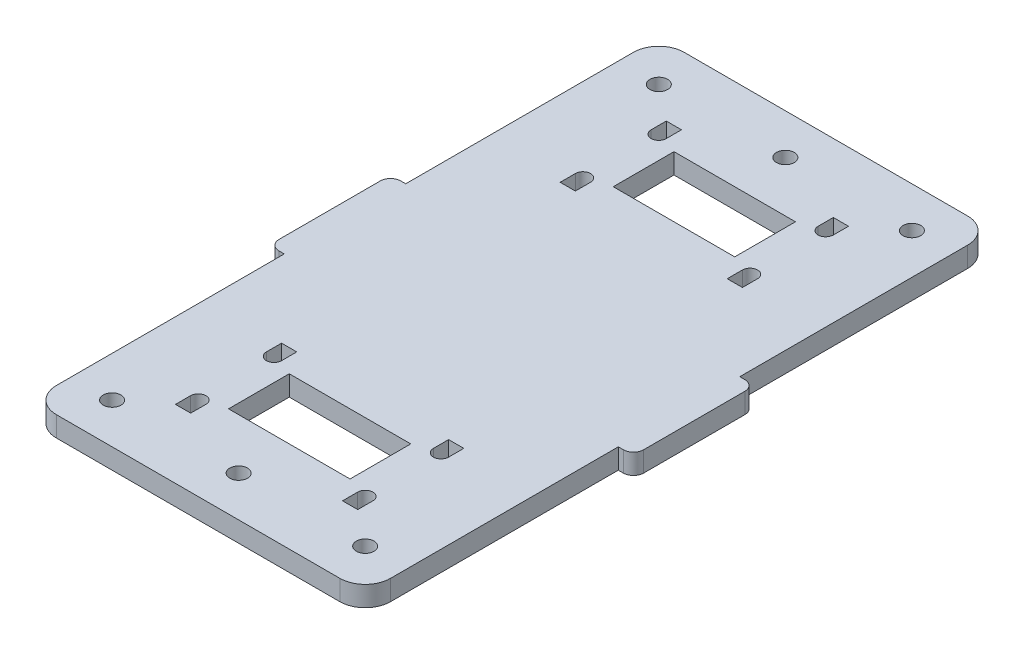
SolidWorks part; units mm, degrees
ref_plane "前视基准面" through (0, 0, 0) normal (0, 0, 1) x (1, 0, 0)
ref_plane "上视基准面" through (0, 0, 0) normal (0, 1, 0) x (1, 0, 0)
ref_plane "右视基准面" through (0, 0, 0) normal (1, 0, 0) x (0, 0, -1)
sketch "草图1" plane through (0, 0, 0) normal (0, 1, 0) x (1, 0, 0)
  line L1 (-36, 50) -> (36, 50)
  line L2 (-36, 50) -> (-36, -50)
  line L3 (-36, -50) -> (36, -50)
  line L4 (36, 50) -> (36, -50)
  line L5 (-36, 50) -> (36, -50) construction
  line L6 (-36, -50) -> (36, 50) construction
  point P0 (0, 0)
  dimension "D1" = 100
  dimension "D2" = 72
extrude "凸台-拉伸1" add sketch "草图1" along normal blind 4
sketch "草图2" plane through (0, 0, 50) normal (0, 0, 1) x (1, 0, 0)
  line L4 (-36, 0) -> (36, 0)
  line L5 (36, 0) -> (36, 4)
  line L6 (36, 4) -> (-36, 4)
  line L7 (-36, 4) -> (-36, 0)
  line L8 (-36, 0) -> (36, 0)
  line L9 (36, 0) -> (36, 4)
  line L10 (36, 4) -> (-36, 4)
  line L11 (-36, 4) -> (-36, 0)
  dimension "D1" = 0
extrude "凸台-拉伸2" add sketch "草图2" along normal blind 24
sketch "草图3" plane through (0, 4, 0) normal (0, 1, 0) x (1, 0, 0)
  line L1 (-36, 50) -> (-33, 50)
  line L2 (-36, 50) -> (-36, 0)
  line L3 (-36, 0) -> (-33, 0)
  line L4 (-33, 50) -> (-33, 0)
  line L5 (36, 50) -> (33, 50)
  line L6 (36, 50) -> (36, 0)
  line L7 (36, 0) -> (33, 0)
  line L8 (33, 50) -> (33, 0)
  line L9 (-36, -74) -> (-33, -74)
  line L10 (-36, -74) -> (-36, -24)
  line L11 (-36, -24) -> (-33, -24)
  line L12 (-33, -74) -> (-33, -24)
  line L13 (36, -74) -> (33, -74)
  line L14 (36, -74) -> (36, -24)
  line L15 (36, -24) -> (33, -24)
  line L16 (33, -74) -> (33, -24)
  dimension "D1" = 50
  dimension "D2" = 3
  dimension "D3" = 3
  dimension "D4" = 50
  dimension "D5" = 3
  dimension "D6" = 3
extrude "切除-拉伸1" cut sketch "草图3" against normal through all both and the other way through all
sketch "草图5" plane through (0, 4, 0) normal (0, 1, 0) x (1, 0, 0)
  line L0 (33, 50) -> (-33, 50) construction
  line L1 (-33, 0) -> (-33, 50) construction
  circle A0 centre (-25, 42) radius 1.75
  dimension "D1" = 3.5
  dimension "D2" = 8
  dimension "D3" = 8
extrude "切除-拉伸2" cut sketch "草图5" against normal through all both and the other way through all
sketch "草图6" plane through (0, 4, 0) normal (0, 1, 0) x (1, 0, 0)
  line L0 (33, 50) -> (-33, 50) construction
  line L1 (33, 50) -> (33, 0) construction
  line L2 (-33, -74) -> (-33, -24) construction
  line L3 (33, -74) -> (-33, -74) construction
  line L4 (33, -24) -> (33, -74) construction
  circle A0 centre (25, 42) radius 1.75
  circle A1 centre (-25, -66) radius 1.75
  circle A2 centre (25, -66) radius 1.75
  dimension "D1" = 3.5
  dimension "D4" = 8
  dimension "D5" = 8
  dimension "D6" = 8
  dimension "D7" = 3.5
  dimension "D8" = 3.5
  dimension "D9" = 8
  dimension "D2" = 8
  dimension "D3" = 8
extrude "切除-拉伸3" cut sketch "草图6" against normal through all both and the other way through all
sketch "草图7" plane through (0, 4, 0) normal (0, 1, 0) x (1, 0, 0)
  line L1 (-12, -56) -> (12, -56)
  line L2 (-12, -56) -> (-12, -44)
  line L3 (-12, -44) -> (12, -44)
  line L4 (12, -56) -> (12, -44)
  line L5 (-12, 20) -> (12, 20)
  line L6 (-12, 20) -> (-12, 32)
  line L7 (-12, 32) -> (12, 32)
  line L8 (12, 20) -> (12, 32)
extrude "切除-拉伸4" cut sketch "草图7" against normal through all both and the other way through all
fillet "圆角1" radius 5 4 edges at (-33, 2, 74) (33, 2, 74) (33, 2, -50) (-33, 2, -50)
fillet "圆角2" radius 2 4 edges at (36, 2, 24) (36, 2, 0) (-36, 2, 24) (-36, 2, 0)
sketch "草图8" plane through (0, 4, 0) normal (0, 1, 0) x (1, 0, 0)
  line L0 (0, 50) -> (0, -74) construction
  line L1 (28, 50) -> (-28, 50) construction
  line L2 (28, -74) -> (-28, -74) construction
  circle A0 centre (0, 42) radius 1.75
  circle A1 centre (0, -66) radius 1.75
  dimension "D1" = 3.5
  dimension "D3" = 3.5
  dimension "D4" = 8
  dimension "D2" = 8
extrude "切除-拉伸5" cut sketch "草图8" against normal through all both and the other way through all
sketch "草图9" plane through (0, 4, 0) normal (0, 1, 0) x (1, 0, 0)
  line L0 (12, 31.9775) -> (12, 33.4775) construction
  line L2 (12, 20) -> (12, 31.9775) construction
  line L3 (12, 31.9775) -> (21, 31.9775) construction
  line L5 (12, 33.4775) -> (12, 38.4775) construction
  line L6 (12, 33.4775) -> (21, 33.4775) construction
  line L7 (12, 33.4775) -> (12, 18.4775) construction
  line L8 (12, 18.4775) -> (25, 18.4775) construction
  line L9 (25, 20) -> (25, 18.4775) construction
  line L10 (15, 33.4775) -> (15, 36.4775)
  line L11 (12, 38.4775) -> (21, 38.4775) construction
  line L12 (12, 38.4775) -> (12, 31.9775) construction
  line L13 (12, 31.9775) -> (21, 31.9775) construction
  line L14 (21, 38.4775) -> (21, 31.9775) construction
  line L15 (15, 36.4775) -> (18, 36.4775)
  line L16 (18, 36.4775) -> (18, 33.4775)
  line L17 (0, 42) -> (0, 25.9975) construction
  line L18 (-18, 36.4775) -> (-18, 33.4775)
  line L19 (-15, 36.4775) -> (-18, 36.4775)
  line L20 (-15, 33.4775) -> (-15, 36.4775)
  line L21 (-36, -12) -> (36, -12) construction
  line L22 (-36, -2) -> (-36, -22) construction
  line L23 (36, -22) -> (36, -2) construction
  line L24 (21, -62.4775) -> (21, -55.9775) construction
  line L25 (12, -55.9775) -> (21, -55.9775) construction
  line L26 (12, -62.4775) -> (12, -55.9775) construction
  line L27 (12, -62.4775) -> (21, -62.4775) construction
  line L28 (12, -57.4775) -> (21, -57.4775) construction
  line L29 (12, -57.4775) -> (12, -62.4775) construction
  line L30 (12, -55.9775) -> (21, -55.9775) construction
  line L31 (12, -55.9775) -> (12, -57.4775) construction
  line L32 (-15, -57.4775) -> (-15, -60.4775)
  line L33 (-15, -60.4775) -> (-18, -60.4775)
  line L34 (-18, -60.4775) -> (-18, -57.4775)
  line L35 (18, -60.4775) -> (18, -57.4775)
  line L36 (15, -60.4775) -> (18, -60.4775)
  line L37 (15, -57.4775) -> (15, -60.4775)
  line L38 (0, 25.9975) -> (18, 25.9975) construction
  line L39 (21, 13.5174) -> (21, 20.0174) construction
  line L40 (12, 20.0174) -> (21, 20.0174) construction
  line L41 (12, 13.5174) -> (12, 20.0174) construction
  line L42 (12, 13.5174) -> (21, 13.5174) construction
  line L43 (12, 18.5174) -> (21, 18.5174) construction
  line L44 (12, 18.5174) -> (12, 13.5174) construction
  line L45 (12, 20.0174) -> (21, 20.0174) construction
  line L46 (12, 20.0174) -> (12, 18.5174) construction
  line L47 (-15, 18.5174) -> (-15, 15.5174)
  line L48 (-15, 15.5174) -> (-18, 15.5174)
  line L49 (-18, 15.5174) -> (-18, 18.5174)
  line L50 (18, 15.5174) -> (18, 18.5174)
  line L51 (15, 15.5174) -> (18, 15.5174)
  line L52 (15, 18.5174) -> (15, 15.5174)
  line L53 (12, -50) -> (30.5234, -50) construction
  line L54 (12, -56) -> (12, -44) construction
  line L55 (12, -44.0225) -> (12, -42.5225) construction
  line L56 (12, -44.0225) -> (21, -44.0225) construction
  line L57 (12, -42.5225) -> (12, -37.5225) construction
  line L58 (12, -42.5225) -> (21, -42.5225) construction
  line L59 (12, -37.5225) -> (21, -37.5225) construction
  line L60 (12, -37.5225) -> (12, -44.0225) construction
  line L61 (12, -44.0225) -> (21, -44.0225) construction
  line L62 (21, -37.5225) -> (21, -44.0225) construction
  line L63 (15, -42.5225) -> (15, -39.5225)
  line L64 (15, -39.5225) -> (18, -39.5225)
  line L65 (18, -39.5225) -> (18, -42.5225)
  line L66 (-18, -39.5225) -> (-18, -42.5225)
  line L67 (-15, -39.5225) -> (-18, -39.5225)
  line L68 (-15, -42.5225) -> (-15, -39.5225)
  arc A0 (15, 33.4775) -> (18, 33.4775) centre (16.5, 33.4775) ccw
  arc A1 (-15, 33.4775) -> (-18, 33.4775) centre (-16.5, 33.4775) cw
  arc A2 (-15, -57.4775) -> (-18, -57.4775) centre (-16.5, -57.4775) ccw
  arc A3 (15, -57.4775) -> (18, -57.4775) centre (16.5, -57.4775) cw
  arc A4 (-15, 18.5174) -> (-18, 18.5174) centre (-16.5, 18.5174) ccw
  arc A5 (15, 18.5174) -> (18, 18.5174) centre (16.5, 18.5174) cw
  arc A6 (15, -42.5225) -> (18, -42.5225) centre (16.5, -42.5225) ccw
  arc A7 (-15, -42.5225) -> (-18, -42.5225) centre (-16.5, -42.5225) cw
  dimension "D1" = 3
  dimension "D2" = 1.5
  dimension "D3" = 3
  dimension "D4" = 5
  dimension "D5" = 9
extrude "切除-拉伸6" cut sketch "草图9" against normal through all both and the other way through all
